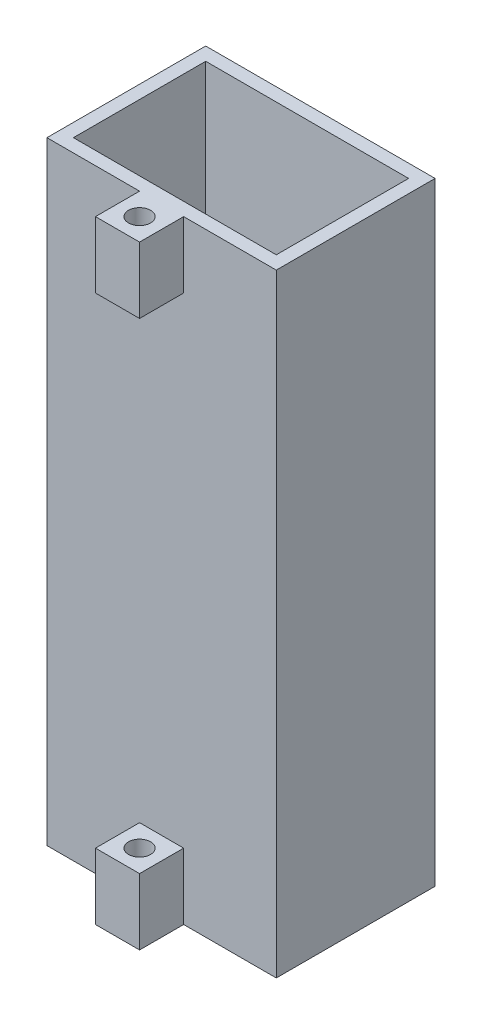
SolidWorks part; units mm, degrees
ref_plane "Front Plane" through (0, 0, 0) normal (0, 0, 1) x (1, 0, 0)
ref_plane "Top Plane" through (0, 0, 0) normal (0, 1, 0) x (1, 0, 0)
ref_plane "Right Plane" through (0, 0, 0) normal (1, 0, 0) x (0, 0, -1)
sketch "Sketch1" plane through (0, 0, 0) normal (0, 1, 0) x (1, 0, 0)
  line L1 (-23, -15) -> (23, -15)
  line L2 (-23, -15) -> (-23, 15)
  line L3 (-23, 15) -> (23, 15)
  line L4 (23, -15) -> (23, 15)
  line L5 (-23, -15) -> (23, 15) construction
  line L6 (-23, 15) -> (23, -15) construction
  line L7 (-26, -18) -> (26, -18)
  line L8 (-26, -18) -> (-26, 18)
  line L9 (-26, 18) -> (26, 18)
  line L10 (26, -18) -> (26, 18)
  line L11 (-26, -18) -> (26, 18) construction
  line L12 (-26, 18) -> (26, -18) construction
  point P0 (0, 0)
  point P6 (0, 0)
  dimension "D1" = 30
  dimension "D2" = 46
  dimension "D3" = 3
  dimension "D4" = 3
extrude "Boss-Extrude1" add sketch "Sketch1" along normal blind 3 contours L7 L10 L9 L8
extrude "Boss-Extrude2" add sketch "Sketch1<3>" along normal blind 136 from surface starting at face at (0, 3, 0)
sketch "Sketch1<3>" plane through (0, 0, 0) normal (0, 1, 0) x (1, 0, 0) same geometry as "Sketch1"
sketch "Sketch2" plane through (0, 0, 18) normal (0, 0, 1) x (1, 0, 0)
  line L0 (-26, 139) -> (26, 139) construction
  line L1 (-5, 124) -> (5, 124)
  line L2 (-5, 124) -> (-5, 139)
  line L3 (-5, 139) -> (5, 139)
  line L4 (5, 124) -> (5, 139)
  line L5 (-5, 124) -> (5, 139) construction
  line L6 (-5, 139) -> (5, 124) construction
  line L7 (-26, 0) -> (26, 0) construction
  line L8 (-5, 15) -> (5, 15)
  line L9 (-5, 15) -> (-5, 0)
  line L10 (-5, 0) -> (5, 0)
  line L11 (5, 15) -> (5, 0)
  line L12 (-5, 15) -> (5, 0) construction
  line L13 (-5, 0) -> (5, 15) construction
  point P0 (0, 131.5)
  point P7 (0, 7.5)
  dimension "D1" = 15
  dimension "D2" = 10
extrude "Boss-Extrude3" add sketch "Sketch2" along normal blind 10
sketch "Sketch3" plane through (0, 139, 0) normal (0, 1, 0) x (1, 0, 0)
  line L0 (-5, -18) -> (5, -28) construction
  circle A0 centre (0, -23) radius 2.5
  point P7 (0, -23)
  dimension "D1" = 5
extrude "Cut-Extrude1" cut sketch "Sketch3" against normal through all both and the other way through all
